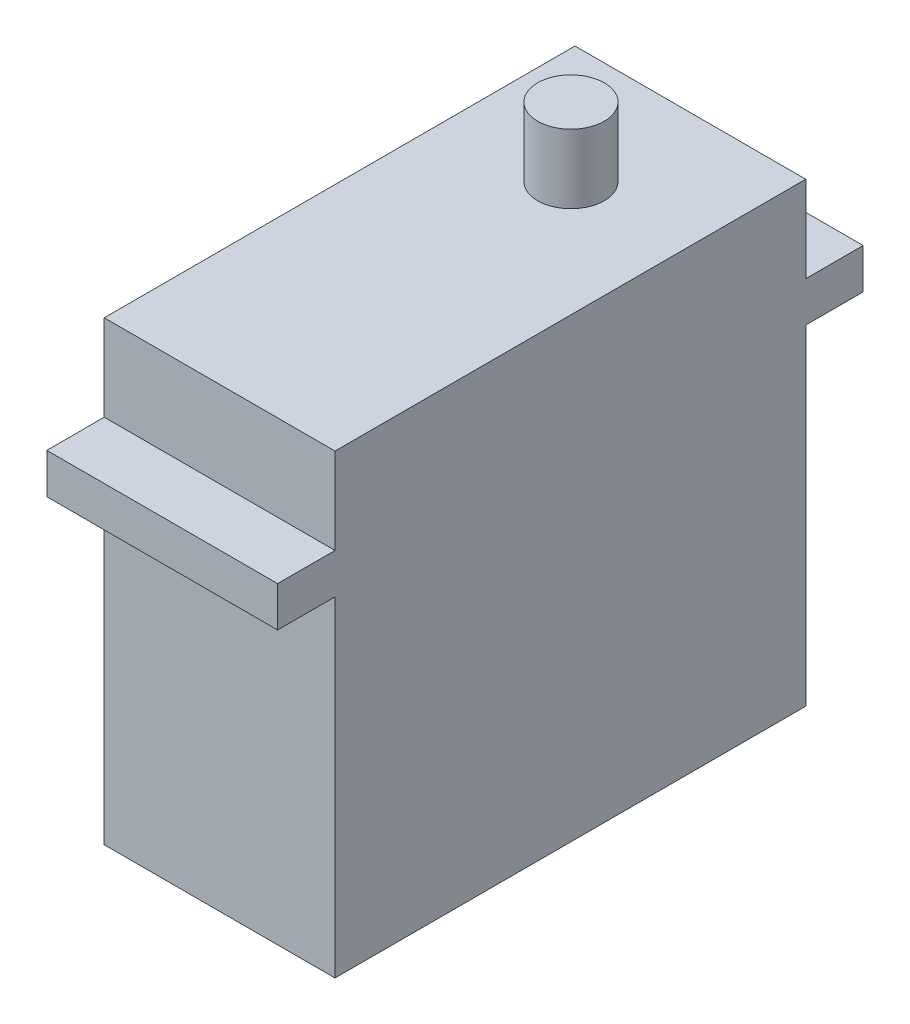
SolidWorks part; units mm, degrees
ref_plane "Front Plane" through (0, 0, 0) normal (0, 0, 1) x (1, 0, 0)
ref_plane "Top Plane" through (0, 0, 0) normal (0, 1, 0) x (1, 0, 0)
ref_plane "Right Plane" through (0, 0, 0) normal (1, 0, 0) x (0, 0, -1)
sketch "Sketch2" plane through (0, 0, 0) normal (1, 0, 0) x (0, 0, -1)
  line L1 (-20.5, 19.875) -> (20.5, 19.875)
  line L2 (-20.5, 19.875) -> (-20.5, -19.875)
  line L3 (-20.5, -19.875) -> (20.5, -19.875)
  line L4 (20.5, 19.875) -> (20.5, -19.875)
  line L5 (-20.5, 19.875) -> (20.5, -19.875) construction
  line L6 (-20.5, -19.875) -> (20.5, 19.875) construction
  line L7 (20.5, 12.375) -> (25.5, 12.375)
  line L8 (20.5, 12.375) -> (20.5, 8.875)
  line L9 (20.5, 8.875) -> (25.5, 8.875)
  line L10 (25.5, 12.375) -> (25.5, 8.875)
  line L11 (-20.5, 12.375) -> (-25.5, 12.375)
  line L12 (-20.5, 12.375) -> (-20.5, 8.875)
  line L13 (-20.5, 8.875) -> (-25.5, 8.875)
  line L14 (-25.5, 12.375) -> (-25.5, 8.875)
  line L16 (-25.5, 10.625) -> (25.5, 10.625) construction
  line L17 (7.2, 19.875) -> (13, 19.875)
  line L18 (7.2, 19.875) -> (7.2, 25.875)
  line L19 (7.2, 25.875) -> (13, 25.875)
  line L20 (13, 19.875) -> (13, 25.875)
  point P0 (0, 0)
  point P22 (0, 10.625)
  dimension "D1" = 32.25
  dimension "D2" = 41
  dimension "D3" = 45.75
  dimension "D4" = 51
  dimension "D5" = 39.75
  dimension "D6" = 3.5
  dimension "D7" = 5.8
  dimension "D8" = 7.5
extrude "Boss-Extrude1" add sketch "Sketch2" along normal blind 20.1 contours L4 L1 L2 L3 | L11 L14 L13 L2 | L1 L20 L19 L18 | L10 L7 L4 L9 region at (0, 0, 0) region at (0, 22.875, -10.1) region at (0, 10.625, 23) region at (0, 10.625, -23)
sketch "Sketch3" plane through (0, 19.875, 0) normal (0, 1, 0) x (1, 0, 0)
  line L0 (20.1, 13) -> (0, 13) construction
  line L1 (20.1, 7.2) -> (12.95, 7.2)
  line L2 (20.1, 7.2) -> (20.1, 13)
  line L3 (20.1, 13) -> (12.95, 13)
  line L4 (12.95, 7.2) -> (12.95, 13)
  line L5 (20.1, 13) -> (0, 13) construction
  line L6 (0, 7.2) -> (7.15, 7.2)
  line L7 (0, 7.2) -> (0, 13)
  line L8 (0, 13) -> (7.15, 13)
  line L9 (7.15, 7.2) -> (7.15, 13)
  line L10 (20.1, 25.5) -> (0, 25.5) construction
  line L11 (12.95, 13) -> (7.15, 13)
  line L12 (12.95, 7.2) -> (7.15, 7.2)
  circle A0 centre (10.05, 10.1) radius 2.9
  point P15 (7.15, 10.1)
  point P21 (10.05, 25.5)
  line M7 (20.1, 7.2) -> (0, 7.2)
extrude "Cut-Extrude1" cut sketch "Sketch3" along normal up to surface (6 mm away) contours A0 L4 M7 | A0 L4 L11 | A0 L11 L9 | A0 L9 L12 | L9 L8 L7 M7 | L4 L2 L3 M7 region at (16.525, 19.875, -10.1) region at (12.3022, 19.875, -7.8478) region at (12.3022, 19.875, -12.3522) region at (7.7978, 19.875, -7.8478) region at (7.7978, 19.875, -12.3522) region at (3.575, 19.875, -10.1) up to face at (10.05, 25.875, -10.1)
